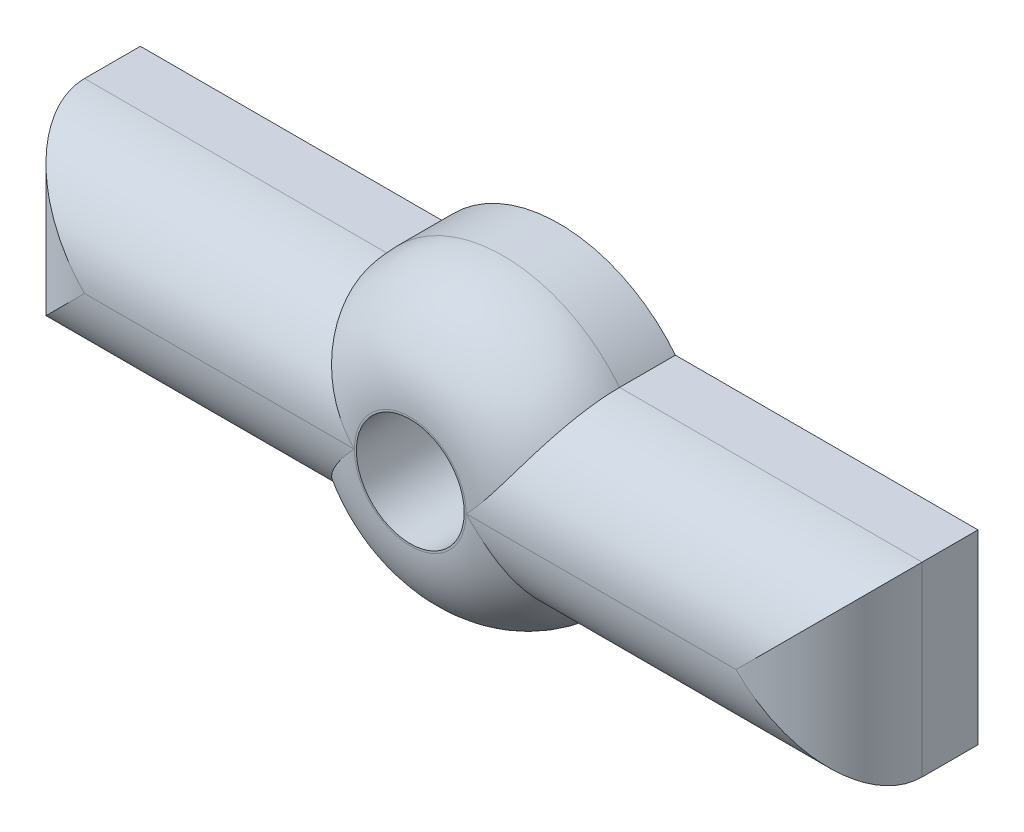
SolidWorks part; units mm, degrees
ref_plane "Plan de face" through (0, 0, 0) normal (0, 0, 1) x (1, 0, 0)
ref_plane "Plan de dessus" through (0, 0, 0) normal (0, 1, 0) x (1, 0, 0)
ref_plane "Plan de droite" through (0, 0, 0) normal (1, 0, 0) x (0, 0, -1)
sketch "Esquisse1" plane through (0, 0, 0) normal (0, 0, 1) x (1, 0, 0)
  line L0 (-22.5, 5) -> (22.5, -5) construction
  line L1 (-22.5, 5) -> (-6.245, 5)
  line L2 (-22.5, 5) -> (-22.5, -5)
  line L3 (-22.5, -5) -> (-6.245, -5)
  line L4 (22.5, 5) -> (22.5, -5)
  line L5 (-22.5, -5) -> (22.5, 5) construction
  line L6 (6.245, 5) -> (22.5, 5)
  line L7 (6.245, -5) -> (22.5, -5)
  arc A0 (6.245, 5) -> (-6.245, 5) centre (0, 0) ccw
  arc A1 (-6.245, -5) -> (6.245, -5) centre (0, 0) ccw
  point P4 (0, 0)
  dimension "D3" = 16
  dimension "D1" = 10
  dimension "D2" = 45
extrude "Boss.-Extru.2" add sketch "Esquisse1" along normal blind 8
fillet "Congé1" radius 5 8 edges at (0, 8, 8) (0, -8, 8) (14.3725, 5, 8) (22.5, 0, 8) (14.3725, -5, 8) (-14.3725, 5, 8) (-14.3725, -5, 8) (-22.5, 0, 8)
hole_wizard "Dégagement #121" positions "Esquisse2" profile "Esquisse3" hole size "#12" standard "Ansi Inch" end condition through all
sketch "Esquisse2" plane through (0, 0, 8) normal (0, 0, 1) x (1, 0, 0)
  point P0 (0, 0)
sketch "Esquisse3" plane through (0, 0, 8) normal (1, 0, 0) x (0, -1, 0)
  line L0 (0, 0) -> (0, 8)
  line L1 (0, 8) -> (2.8956, 8)
  line L2 (2.8956, 8) -> (2.8956, 0)
  line L5 (2.8956, 0) -> (0, 0)
  line L11 (0, -6.35) -> (0, 107.95) construction
  dimension "Diamètre du perçage jusqu'au prochain" = 5.7912
  dimension "Profondeur du perçage jusqu'au prochain" = 8
